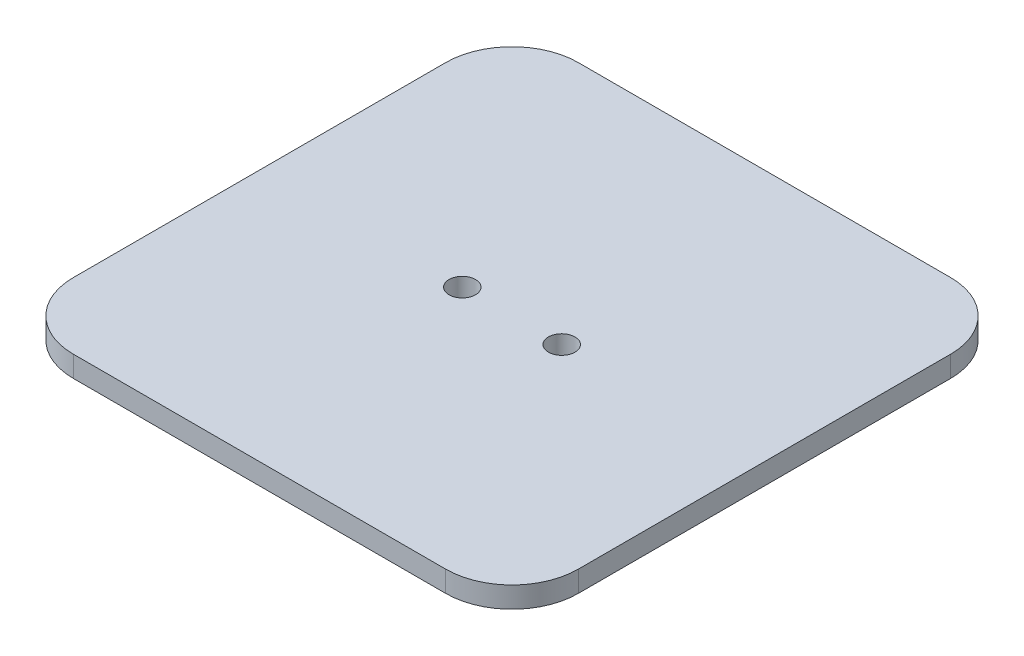
SolidWorks part; units mm, degrees
ref_plane "Front Plane" through (0, 0, 0) normal (0, 0, 1) x (1, 0, 0)
ref_plane "Top Plane" through (0, 0, 0) normal (0, 1, 0) x (1, 0, 0)
ref_plane "Right Plane" through (0, 0, 0) normal (1, 0, 0) x (0, 0, -1)
sketch "Sketch1" plane through (0, 0, 0) normal (0, 1, 0) x (1, 0, 0)
  line L1 (-38.1, -38.1) -> (38.1, -38.1)
  line L2 (-38.1, -38.1) -> (-38.1, 38.1)
  line L3 (-38.1, 38.1) -> (38.1, 38.1)
  line L4 (38.1, -38.1) -> (38.1, 38.1)
  line L5 (-38.1, -38.1) -> (38.1, 38.1) construction
  line L6 (-38.1, 38.1) -> (38.1, -38.1) construction
  point P0 (0, 0)
  dimension "D1" = 76.2
  dimension "D2" = 76.2
extrude "Boss-Extrude1" add sketch "Sketch1" along normal blind 3.175
fillet "Fillet1" radius 10 1 edges at (-38.1, 1.5875, 38.1)
fillet "Fillet2" radius 10 1 edges at (-38.1, 1.5875, -38.1)
fillet "Fillet3" radius 10 1 edges at (38.1, 1.5875, -38.1)
fillet "Fillet4" radius 10 1 edges at (38.1, 1.5875, 38.1)
sketch "Sketch2" plane through (0, 3.175, 0) normal (0, 1, 0) x (1, 0, 0)
  line L0 (-1.7463, 0) -> (1.7463, 0) construction
  line L1 (38.1, -28.1) -> (38.1, 28.1) construction
  circle A0 centre (7.5, 0) radius 2
  circle A1 centre (-7.5, 0) radius 2
  dimension "D1" = 4
  dimension "D2" = 4
  dimension "D3" = 15
  dimension "D4" = 30.6
extrude "Cut-Extrude1" cut sketch "Sketch2" against normal through all
